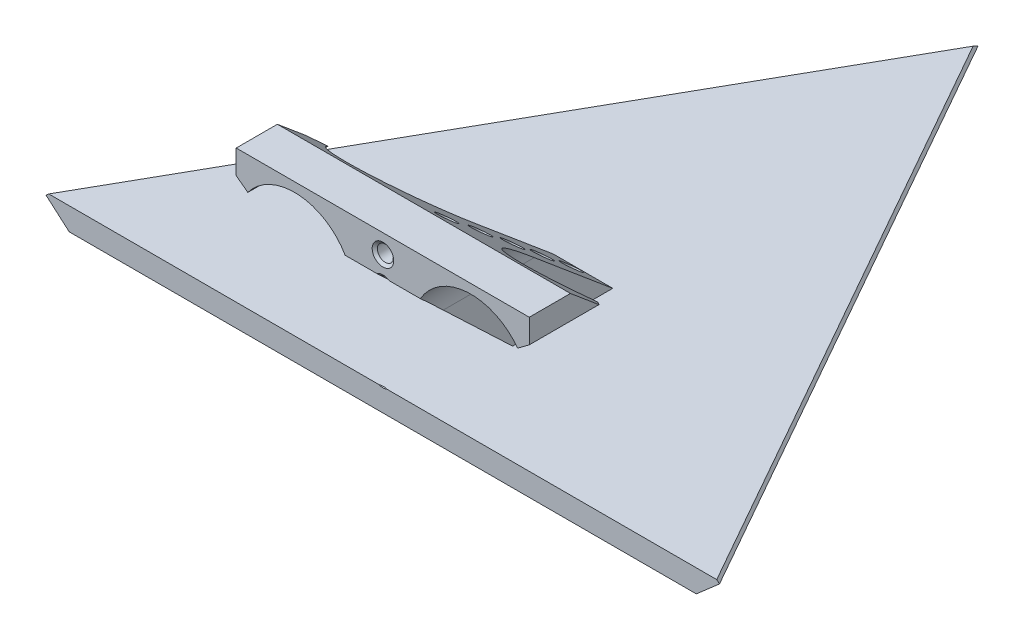
SolidWorks part; units mm, degrees
ref_plane "Front Plane" through (0, 0, 0) normal (0, 0, 1) x (1, 0, 0)
ref_plane "Top Plane" through (0, 0, 0) normal (0, 1, 0) x (1, 0, 0)
ref_plane "Right Plane" through (0, 0, 0) normal (1, 0, 0) x (0, 0, -1)
sketch "Sketch1" plane through (0, 0, 0) normal (0, 0, 1) x (1, 0, 0)
  line L24 (-5.4349, -5.4971) -> (-1.8428, -9.0893)
  line L25 (-1.8428, -10.8853) -> (-7.9749, -10.8853)
  line L26 (1.7493, -10.8853) -> (1.7493, -9.0893)
  line L28 (-5.4349, -5.4971) -> (-5.4349, -0.3871)
  line L29 (5.3414, -5.4971) -> (5.3414, -0.3871)
  line L30 (7.8814, -10.8853) -> (1.7493, -10.8853)
  line L31 (1.7493, -10.8853) -> (1.7493, -9.0893)
  line L32 (1.7493, -9.0893) -> (5.3414, -5.4971)
  line L34 (-1.8428, -9.0893) -> (-1.8428, -10.8853)
  line L37 (7.8814, -10.8853) -> (7.8814, -0.3871)
  line L38 (-5.4349, -0.3871) -> (5.3414, -0.3871)
  line L39 (-7.9749, -10.8853) -> (-7.9749, -0.3871)
  line L41 (-5.4349, -0.3871) -> (5.3414, -0.3871)
  line L42 (-7.9749, -0.3871) -> (-7.9749, 0.5865)
  line L43 (-7.9749, 0.5865) -> (7.8814, 0.5865)
  line L44 (7.8814, -0.3871) -> (7.8814, 0.5865)
ref_plane "Plane1" through (0, 0, 0) normal (0, 0, 1) x (1, 0, 0)
sketch "Sketch2" plane through (0, 0, 0) normal (0, 0, 1) x (1, 0, 0)
  line L0 (-7.9749, 0.5865) -> (-7.9749, -10.8853)
  line L1 (-7.9749, -10.8853) -> (-1.9428, -10.8853)
  line L9 (1.8493, -10.8853) -> (7.8814, -10.8853)
  line L10 (7.8814, -10.8853) -> (7.8814, 0.5865)
  line L11 (7.8814, 0.5865) -> (-7.9749, 0.5865)
  line L13 (-5.5349, -0.3871) -> (-5.5349, -5.4971)
  line L15 (-1.9428, -9.0893) -> (-5.5349, -5.4971)
  line L16 (-1.9428, -9.0893) -> (-1.9428, -10.8853)
  line L17 (5.4414, -0.3871) -> (5.4414, -0.2871)
  line L18 (5.4414, -0.2871) -> (-5.5349, -0.2871)
  line L19 (5.4414, -5.4971) -> (5.4414, -0.3871)
  line L21 (1.8493, -9.0893) -> (5.4414, -5.4971)
  line L22 (1.8493, -9.0893) -> (1.8493, -10.8853)
  line L23 (-5.5349, -0.2871) -> (-5.5349, -0.3871)
extrude "Boss-Extrude1" add sketch "Sketch2" along normal blind 7.65
sketch "Sketch3" plane through (0, 0.5865, 0) normal (0, 1, 0) x (1, 0, 0)
  line L3 (-0.0467, -58.45) -> (76.1533, -58.45)
  line L4 (76.1533, -58.45) -> (0, 76.2)
  line L5 (-0.0467, -58.45) -> (-76.2467, -58.45)
  line L6 (-76.2467, -58.45) -> (0, 76.2)
extrude "Boss-Extrude2" add sketch "Sketch3" along normal blind 5.08
chamfer "Chamfer1" distance 1 angle 45 1 edges at (38.0766, 5.6665, -8.875)
chamfer "Chamfer2" distance 1 angle 45 1 edges at (-38.4108, 5.6665, -8.3675)
chamfer "Chamfer3" distance 5 angle 45 1 edges at (-38.1234, 0.5865, -8.875)
chamfer "Chamfer4" distance 5 angle 45 1 edges at (39.5122, 0.5865, -6.3366)
sketch "Sketch4" plane through (0, 5.6665, 0) normal (0, 1, 0) x (1, 0, 0)
  line L1 (-75.0976, -58.45) -> (75.0044, -58.45) construction
  line L2 (-7.9749, -13.45) -> (7.8814, -13.45)
  line L4 (7.8814, -58.45) -> (-7.9749, -58.45)
  line L5 (-7.9749, -58.45) -> (-32.9749, -58.45)
  line L6 (-32.9749, -58.45) -> (-32.9749, -13.45)
  line L7 (-32.9749, -13.45) -> (-7.9749, -13.45)
  line L8 (7.8814, -13.45) -> (32.8814, -13.45)
  line L9 (32.8814, -13.45) -> (32.8814, -58.45)
  line L10 (32.8814, -58.45) -> (7.8814, -58.45)
extrude "Boss-Extrude3" add sketch "Sketch4" along normal blind 30 contours L4 L5 L6 L7 L2 L8 L9 L10
sketch "Sketch5" plane through (0, 0, 13.45) normal (0, 0, -1) x (-1, 0, 0)
  line L10 (-6.6407, 5.6665) -> (-32.8814, 5.6665)
  line L11 (-32.8814, 35.6665) -> (-32.8814, 5.6665) construction
  line L18 (-32.8814, 30.2857) -> (-32.8814, 5.6665)
  line L21 (-32.8814, 30.2857) -> (-6.6407, 10.6665)
  line L22 (6.7342, 10.6665) -> (6.7342, 5.6665)
  line L25 (6.7342, 10.6665) -> (32.9749, 30.2857)
  line L26 (32.9749, 35.6665) -> (32.9749, 5.6665) construction
  line L27 (32.9749, 30.2857) -> (32.9749, 5.6665)
  line L28 (32.9749, 5.6665) -> (6.7342, 5.6665)
  line L29 (-6.6407, 10.6665) -> (-6.6407, 5.6665)
extrude "Cut-Extrude1" cut sketch "Sketch5" against normal blind 45.08
sketch "Sketch7" plane through (0, 0, 13.45) normal (0, 0, -1) x (-1, 0, 0)
  line L0 (32.9749, 30.2857) -> (6.7342, 10.6665) construction
  line L1 (-6.6407, 10.6665) -> (-32.8814, 30.2857) construction
  line L2 (-6.6407, 20.4761) -> (-6.6407, 10.6665)
  line L3 (-6.6407, 10.6665) -> (-11.0482, 10.6665)
  line L4 (6.7342, 20.4761) -> (6.7342, 10.6665)
  line L5 (6.7342, 10.6665) -> (11.1417, 10.6665)
  arc A2 (-6.6407, 20.4761) -> (-11.0482, 10.6665) centre (-19.7611, 20.4761) ccw
  arc A3 (11.1417, 10.6665) -> (6.7342, 20.4761) centre (19.8546, 20.4761) ccw
extrude "Cut-Extrude3" cut sketch "Sketch7" against normal blind 45.08
sketch "Sketch9" plane through (-6.7342, 0, 0) normal (-1, 0, 0) x (0, 0, 1)
  line L0 (13.45, 5.6665) -> (49.2026, 35.6665)
  line L1 (58.45, 35.6665) -> (13.45, 35.6665) construction
  line L2 (49.2026, 35.6665) -> (13.45, 35.6665)
  line L3 (13.45, 35.6665) -> (13.45, 5.6665)
extrude "Cut-Extrude4" cut sketch "Sketch9" against normal through all both and the other way through all
hole_wizard "9/64 (0.14063) Diameter Hole1" positions "Sketch10" profile "Sketch11" hole size "9/64" standard "ANSI Inch" end condition up to next
sketch "Sketch10" plane through (0, 0, 58.45) normal (0, 0, 1) x (1, 0, 0)
  point P0 (0, 31.4082)
  point P2 (0, 25.0462)
  point P4 (0, 18.9945)
  point P6 (0, 13.4083)
  point P8 (0, 7.8997)
sketch "Sketch11" plane through (0, 31.4082, 58.45) normal (1, 0, 0) x (0, -1, 0)
  line L0 (0, 0) -> (0, 14.3222)
  line L1 (0, 14.3222) -> (1.786, 14.3222)
  line L2 (1.786, 14.3222) -> (1.786, 0.5328)
  line L3 (1.786, 0.5328) -> (2.421, 0)
  line L5 (2.421, 0) -> (0, 0)
  line L6 (-1.786, 0.5328) -> (-2.421, 0) construction
  line L11 (0, -6.35) -> (0, 107.95) construction
  dimension "Thru Hole Dia." = 3.572
  dimension "Thru Hole Depth" = 14.3222
  dimension "Near C'Sink Dia." = 4.842
  dimension "Near C'Sink Angle" = 100
sketch "Sketch13" plane through (6.6407, 0, 0) normal (1, 0, 0) x (0, 0, -1)
  line L0 (-58.45, 27.0362) -> (-35.95, 5.6665)
  line L1 (-58.45, 33.5964) -> (-58.45, 20.4761) construction
  line L2 (-58.45, 5.6665) -> (-13.45, 5.6665) construction
  line L3 (-35.95, 5.6665) -> (-58.45, 5.6665)
  line L4 (-58.45, 5.6665) -> (-58.45, 27.0362)
extrude "Cut-Extrude5" cut sketch "Sketch13" against normal through all both and the other way through all
